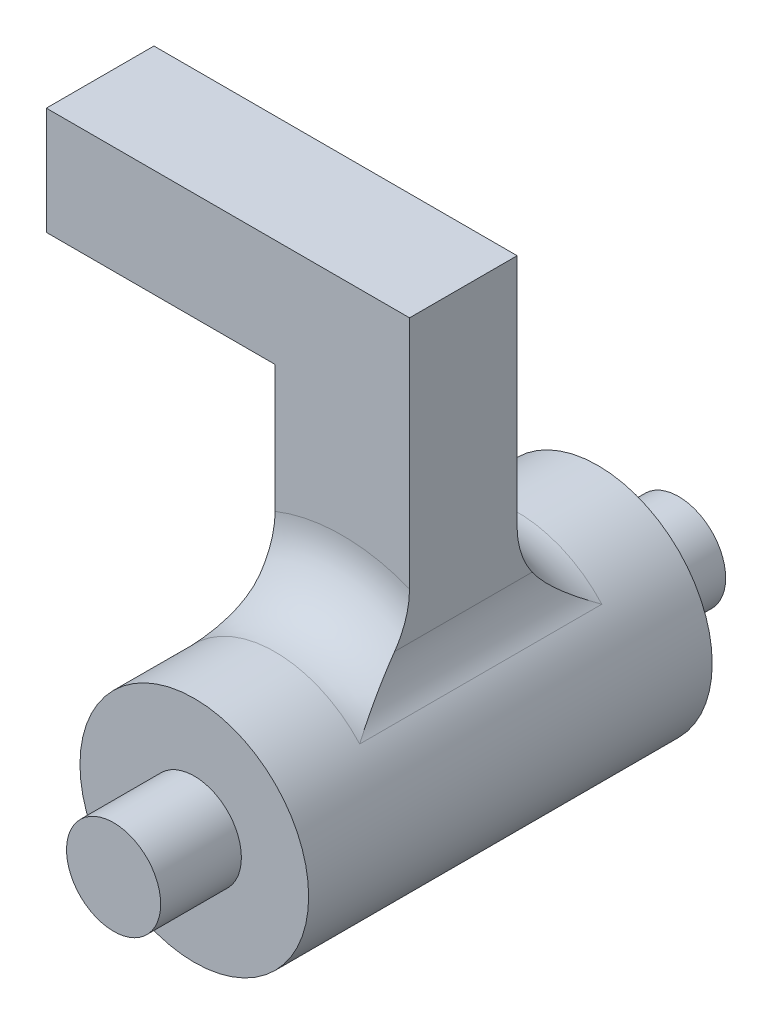
SolidWorks part; units mm, degrees
ref_plane "Front Plane" through (0, 0, 0) normal (0, 0, 1) x (1, 0, 0)
ref_plane "Top Plane" through (0, 0, 0) normal (0, 1, 0) x (1, 0, 0)
ref_plane "Right Plane" through (0, 0, 0) normal (1, 0, 0) x (0, 0, -1)
sketch "Sketch1" plane through (0, 0, 0) normal (0, 0, 1) x (1, 0, 0)
  circle A1 centre (0, 0) radius 8.5
extrude "Boss-Extrude1" add sketch "Sketch1" along normal blind 15 and the other way blind 15
sketch "Sketch2" plane through (0, 0, 0) normal (0, 0, 1) x (1, 0, 0)
  line L2 (-5, 6.8739) -> (-5, 30)
  line L3 (-5, 30) -> (5, 30)
  line L4 (5, 6.8739) -> (5, 30)
  arc A0 (5, 6.8739) -> (-5, 6.8739) centre (0, 0) ccw
  dimension "D2" = 10
extrude "Boss-Extrude2" add sketch "Sketch2" along normal blind 4 and the other way blind 4
fillet "Fillet1" radius 5 4 edges at (0, 8.5, -4) (-5, 6.8739, 0) (0, 8.5, 4) (5, 6.8739, 0)
sketch "Sketch3" plane through (-5, 0, 0) normal (-1, 0, 0) x (0, 0, 1)
  line L0 (4, 30) -> (4, 12.5399) construction
  line L1 (-4, 30) -> (4, 30)
  line L2 (-4, 30) -> (-4, 22)
  line L3 (-4, 22) -> (4, 22)
  line L4 (4, 30) -> (4, 22)
  dimension "D1" = 8
extrude "Boss-Extrude3" add sketch "Sketch3" along normal blind 17
sketch "Sketch4" plane through (0, 0, 15) normal (0, 0, 1) x (1, 0, 0)
  circle A0 centre (0, 0) radius 3.5
extrude "Boss-Extrude4" add sketch "Sketch4" along normal blind 6 and the other way blind 36
